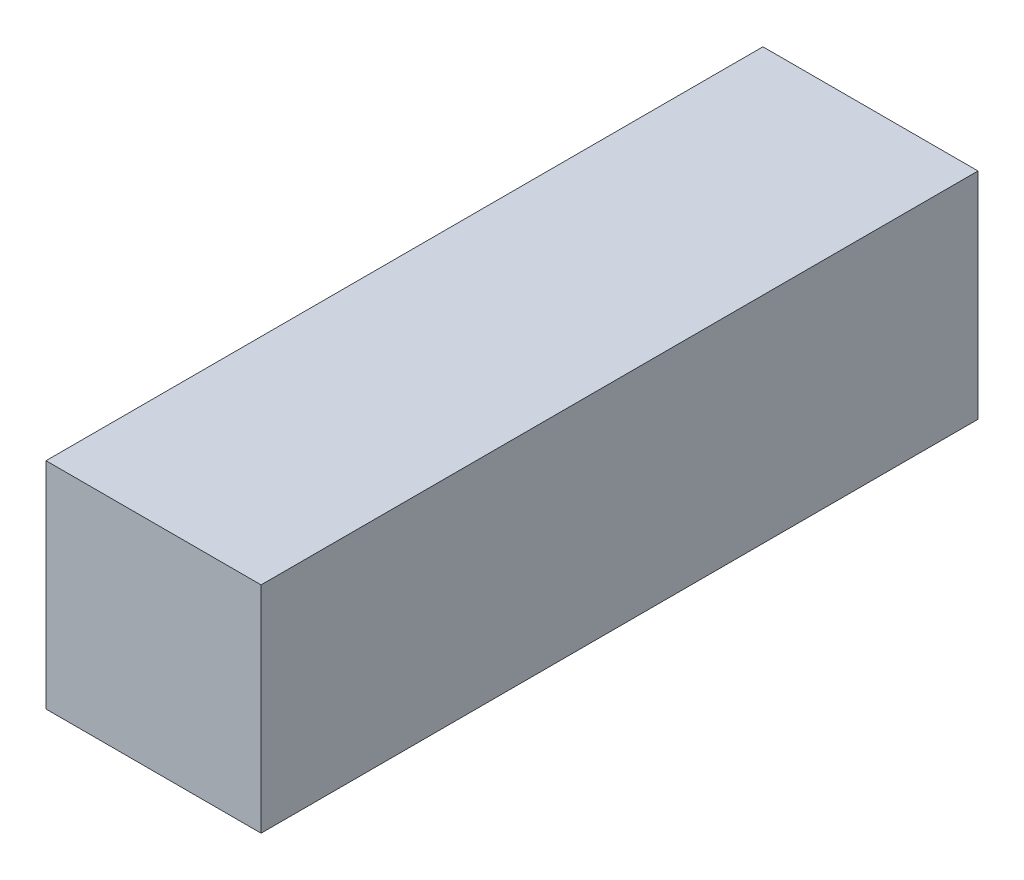
SolidWorks part; units mm, degrees
material "Pine"
ref_plane "Front Plane" through (0, 0, 0) normal (0, 0, 1) x (1, 0, 0)
ref_plane "Top Plane" through (0, 0, 0) normal (0, 1, 0) x (1, 0, 0)
ref_plane "Right Plane" through (0, 0, 0) normal (1, 0, 0) x (0, 0, -1)
sketch "Sketch1" plane through (0, 0, 0) normal (0, 0, 1) x (1, 0, 0)
  line L1 (-8.7312, 31.8492) -> (29.3688, 31.8492)
  line L2 (-8.7312, 31.8492) -> (-8.7312, -6.2508)
  line L3 (-8.7312, -6.2508) -> (29.3688, -6.2508)
  line L4 (29.3688, 31.8492) -> (29.3688, -6.2508)
  dimension "D1" = 38.1
  dimension "D2" = 38.1
extrude "Boss-Extrude1" add sketch "Sketch1" along normal blind 127
